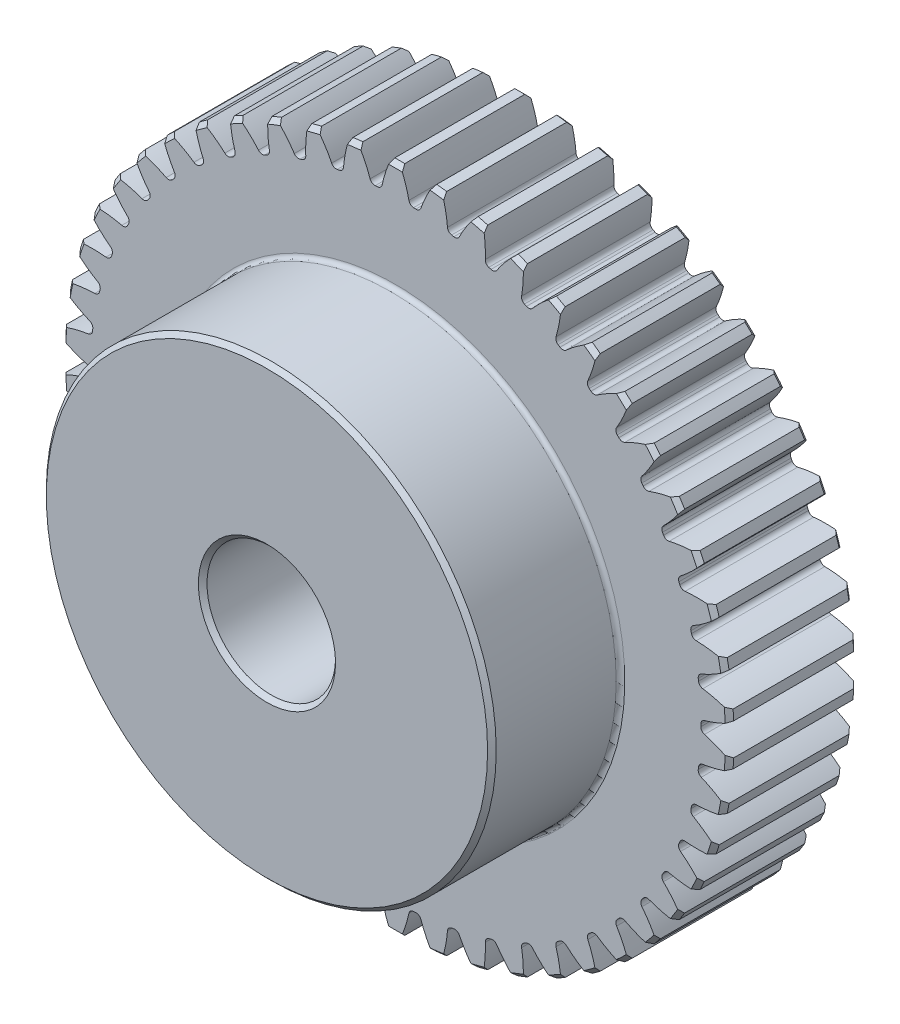
SolidWorks part; units mm, degrees
ref_plane "Front Plane" through (0, 0, 0) normal (0, 0, 1) x (1, 0, 0)
ref_plane "Top Plane" through (0, 0, 0) normal (0, 1, 0) x (1, 0, 0)
ref_plane "Right Plane" through (0, 0, 0) normal (1, 0, 0) x (0, 0, -1)
sketch "Sketch1" plane through (0, 0, 0) normal (0, 0, 1) x (1, 0, 0)
  line L0 (0, 0) -> (0, 25) construction
  line L1 (-8.0348, 27.9244) -> (8.0348, 22.0756) construction
  circle A0 centre (0, 0) radius 23.75 construction
  circle A1 centre (0, 0) radius 26 construction
  circle A2 centre (0, 0) radius 25 construction
  circle A3 centre (0, 0) radius 23.4923 construction
  circle A4 centre (0, 0) radius 17.5 construction
  circle A5 centre (0, 0) radius 5 construction
  point P8 (0.5, 0)
  point P13 (25, 0)
  dimension "OD" = 52
  dimension "Root Diameter" = 47.5
  dimension "Gear Pitch Diameter" = 50
  dimension "Base Diameter" = 46.9846
  dimension "Hub Diameter" = 35
  dimension "For Shaft Diameter" = 10
  dimension "Pressure Angle" = 20
  dimension "Number of Teeth" = 50
  dimension "Module" = 1
sketch "Sketch2" plane through (0, 0, 0) normal (1, 0, 0) x (0, 0, -1)
  line L0 (-10, 0) -> (10, 0) construction
  line L1 (10, 26) -> (10, -26) construction
  line L2 (0, -17.5) -> (-10, -17.5) construction
  line L3 (-10, 26) -> (10, 26) construction
  line L8 (-10, -17.5) -> (-10, 17.5) construction
  point P4 (0, 26)
  point P5 (-5, 0)
  dimension "Overall Width" = 20
  dimension "Hub Width" = 10
  dimension "Approx Set Screw Positon" = 5
  dimension "Face Width" = 10
sketch "Sketch3" plane through (0, 0, 0) normal (0, 0, 1) x (1, 0, 0)
  circle A0 centre (0, 0) radius 26
  circle A1 centre (0, 0) radius 26 construction
extrude "Boss-Extrude1" add sketch "Sketch3" against normal up to vertex (10 mm away) and the other way up to vertex (10 mm away) up to point (0, 0, -10) other way up to point (0, 0, 10)
sketch "Sketch5" plane through (0, 0, 0) normal (1, 0, 0) x (0, 0, -1)
  line L1 (0, 17.5) -> (-10, 17.5)
  line L2 (0, 17.5) -> (0, 26)
  line L3 (0, 26) -> (-10, 26)
  line L4 (-10, 17.5) -> (-10, 26)
  line L5 (-10, 0) -> (10, 0)
  line L6 (-10, 0) -> (-10, 5)
  line L7 (-10, 5) -> (10, 5)
  line L8 (10, 0) -> (10, 5)
  point P5 (0, 17.5)
  point P12 (0, 5)
revolve "Cut-Revolve1" cut sketch "Sketch5" angle 360 about L0
fillet "Fillet2" radius 0.3355 1 edges at (0, -17.5, 0)
chamfer "Chamfer1" distance 0.3355 angle 45 5 edges at (0, -5, -10) (0, -26, 0) (26, 0, -10) (0, -5, 10) (0, -17.5, 10)
sketch "Sketch4" plane through (0, 0, 0) normal (0, 0, 1) x (1, 0, 0)
  line L0 (23.7468, 0.3927) -> (23.7468, -0.3927)
  arc A3 (25.9702, 1.2454) -> (25.9702, -1.2454) centre (0, 0) cw
  circle A4 centre (0, 0) radius 26 construction
  arc A5 (23.7468, 0.3927) -> (25.9702, 1.2454) centre (21.4516, 9.7019) ccw
  circle A8 centre (0, 0) radius 23.75 construction
  arc A9 (23.7468, -0.3927) -> (25.9702, -1.2454) centre (21.4516, -9.7019) cw
  spline S0 degree 4 poles (23.4891, 0.3879) (23.493, 0.388) (23.504, 0.3884) (23.5247, 0.3897) (23.5584, 0.3924) (23.6014, 0.3969) (23.6569, 0.4038) (23.7223, 0.4135) (23.7941, 0.4257) (23.8721, 0.4406) (23.9499, 0.4569) (24.0275, 0.4746) (24.1047, 0.4935) (24.1981, 0.5179) (24.3101, 0.5491) (24.4407, 0.5886) (24.5888, 0.6369) (24.7394, 0.6899) (24.8875, 0.7452) (25.0368, 0.8046) (25.1811, 0.8646) (25.3308, 0.9305) (25.4688, 0.9933) (25.6231, 1.0677) (25.7476, 1.1289) (25.9114, 1.2139) (26.008, 1.2654) (26.121, 1.3272) (26.1712, 1.3555) (26.202, 1.3728) knots 0 0 0 0 0 0.005377 0.015084 0.028532 0.04661 0.064855 0.092111 0.119476 0.146842 0.174209 0.201575 0.228941 0.256307 0.307035 0.361767 0.4165 0.471232 0.525964 0.580697 0.635429 0.690161 0.744894 0.799626 0.854358 0.909091 0.954545 1 1 1 1 1 construction
  spline S1 degree 4 poles (23.4891, 0.3879) (23.493, 0.388) (23.504, 0.3884) (23.5247, 0.3897) (23.5584, 0.3924) (23.6014, 0.3969) (23.6569, 0.4038) (23.7223, 0.4135) (23.7941, 0.4257) (23.8721, 0.4406) (23.9499, 0.4569) (24.0275, 0.4746) (24.1047, 0.4935) (24.1981, 0.5179) (24.3101, 0.5491) (24.4407, 0.5886) (24.5888, 0.6369) (24.7394, 0.6899) (24.8875, 0.7452) (25.0368, 0.8046) (25.1811, 0.8646) (25.3308, 0.9305) (25.4688, 0.9933) (25.6231, 1.0677) (25.7476, 1.1289) (25.8759, 1.1955) (25.9383, 1.2284) (25.9702, 1.2454) knots 0 0 0 0 0 0.005377 0.015084 0.028532 0.04661 0.064855 0.092111 0.119476 0.146842 0.174209 0.201575 0.228941 0.256307 0.307035 0.361767 0.4165 0.471232 0.525964 0.580697 0.635429 0.690161 0.744894 0.799626 0.854358 0.909091 0.909091 0.909091 0.909091 0.909091 construction
  spline S2 degree 4 poles (23.4891, -0.3879) (23.493, -0.388) (23.504, -0.3884) (23.5247, -0.3897) (23.5584, -0.3924) (23.6014, -0.3969) (23.6569, -0.4038) (23.7223, -0.4135) (23.7941, -0.4257) (23.8721, -0.4406) (23.9499, -0.4569) (24.0275, -0.4746) (24.1047, -0.4935) (24.1981, -0.5179) (24.3101, -0.5491) (24.4407, -0.5886) (24.5888, -0.6369) (24.7394, -0.6899) (24.8875, -0.7452) (25.0368, -0.8046) (25.1811, -0.8646) (25.3308, -0.9305) (25.4688, -0.9933) (25.6231, -1.0677) (25.7476, -1.1289) (25.9114, -1.2139) (26.008, -1.2654) (26.121, -1.3272) (26.1712, -1.3555) (26.202, -1.3728) knots 0 0 0 0 0 0.005377 0.015084 0.028532 0.04661 0.064855 0.092111 0.119476 0.146842 0.174209 0.201575 0.228941 0.256307 0.307035 0.361767 0.4165 0.471232 0.525964 0.580697 0.635429 0.690161 0.744894 0.799626 0.854358 0.909091 0.954545 1 1 1 1 1 construction
  spline S3 degree 4 poles (23.4891, -0.3879) (23.493, -0.388) (23.504, -0.3884) (23.5247, -0.3897) (23.5584, -0.3924) (23.6014, -0.3969) (23.6569, -0.4038) (23.7223, -0.4135) (23.7941, -0.4257) (23.8721, -0.4406) (23.9499, -0.4569) (24.0275, -0.4746) (24.1047, -0.4935) (24.1981, -0.5179) (24.3101, -0.5491) (24.4407, -0.5886) (24.5888, -0.6369) (24.7394, -0.6899) (24.8875, -0.7452) (25.0368, -0.8046) (25.1811, -0.8646) (25.3308, -0.9305) (25.4688, -0.9933) (25.6231, -1.0677) (25.7476, -1.1289) (25.8759, -1.1955) (25.9383, -1.2284) (25.9702, -1.2454) knots 0 0 0 0 0 0.005377 0.015084 0.028532 0.04661 0.064855 0.092111 0.119476 0.146842 0.174209 0.201575 0.228941 0.256307 0.307035 0.361767 0.4165 0.471232 0.525964 0.580697 0.635429 0.690161 0.744894 0.799626 0.854358 0.909091 0.909091 0.909091 0.909091 0.909091 construction
  dimension "D1" = 0.7854
extrude "Cut-Extrude1" cut sketch "Sketch4" against normal through all both and the other way through all
fillet "Fillet1" radius 0.3927 2 edges at (23.7468, 0.3927, -5) (23.7468, -0.3927, -5)
pattern_circular "CirPattern1" count 50 over 360 about axis through (0, 0, 10) along (0, 0, -1) of "Cut-Extrude1", "Fillet1"
equation "\"Number of Teeth\"= 50"
equation "\"Module\"= 1"
equation "\"Diametral Pitch\"= 1 / \"Module\""
equation "\"Dedendum\"= 1.25 / \"Diametral Pitch\""
equation "\"Pitch Diameter\"= \"Module\" * \"Number of Teeth\""
equation "\"Root Diameter\"= \"Pitch Diameter\" - ( 2 * \"Dedendum\" )"
equation "\"Root Diameter@Sketch1\"=\"Root Diameter\""
equation "\"OD@Sketch1\" = \"Outside Diameter\""
equation "\"D1@CirPattern1\"=\"Number of Teeth\""
equation "\"Pressure Angle\"=20"
equation "\"Base Diameter\"= \"Pitch Diameter\" * cos ( \"Pressure Angle\" )"
equation "\"Outside Diameter\"= ( \"Number of Teeth\" + 2 ) / \"Diametral Pitch\""
equation "\"Pitch Angle\"= 360deg / \"Number of Teeth\""
equation "\"Alpha\"= sqr ( \"Pitch Diameter\" ^ 2 - \"Base Diameter\" ^ 2 ) / \"Base Diameter\" * 180 / PI - \"Pressure Angle\""
equation "\"Beta\"= ( \"Pitch Angle\" / 4 - \"Alpha\" )"
equation "\"Phi\"= sqr ( ( \"Outside Diameter\" / 2 ) ^ 2 - ( \"Base Diameter\" / 2 ) ^ 2 ) / ( \"Base Diameter\" / 2 )"
equation "\"Addendum\"= 1 / \"Diametral Pitch\""
equation "\"WorkingDepth\"= 2 / \"Diametral Pitch\""
equation "\"WholeDepth\"= 2.25 / \"Diametral Pitch\""
equation "\"Clearance\"= 0.25 / \"Diametral Pitch\""
equation "\"ToothThickness\"= ( pi * 2 ) / \"Diametral Pitch\""
equation "\"CircularPitch\"= pi / \"Diametral Pitch\""
equation "\"Number of Teeth@Sketch1\"=\"Number of Teeth\""
equation "\"Module@Sketch1\"=\"Module\""
equation "\"Pressure Angle@Sketch1\"=\"Pressure Angle\""
equation "\"Gear Pitch Diameter@Sketch1\"=\"Pitch Diameter\""
equation "\"Base Diameter@Sketch1\"=\"Base Diameter\""
equation "\"Fillet\"= \"Clearance\" * cos ( \"Pressure Angle\" ) * tan ( ( 90 + \"Pressure Angle\" ) / 2 )"
equation "\"D1@Fillet2\"=\"Fillet\""
equation "\"Approx Set Screw Positon@Sketch2\" = \"Hub Width@Sketch2\" / 2"
equation "\"D2\"= \"Fillet\" * 2"
equation "\"D1@Chamfer1\"=\"Fillet\""
equation "\"D1@Sketch4\"=\"CircularPitch\"*0.25"
equation "\"D1@Fillet1\"=\"CircularPitch\"*0.125"
